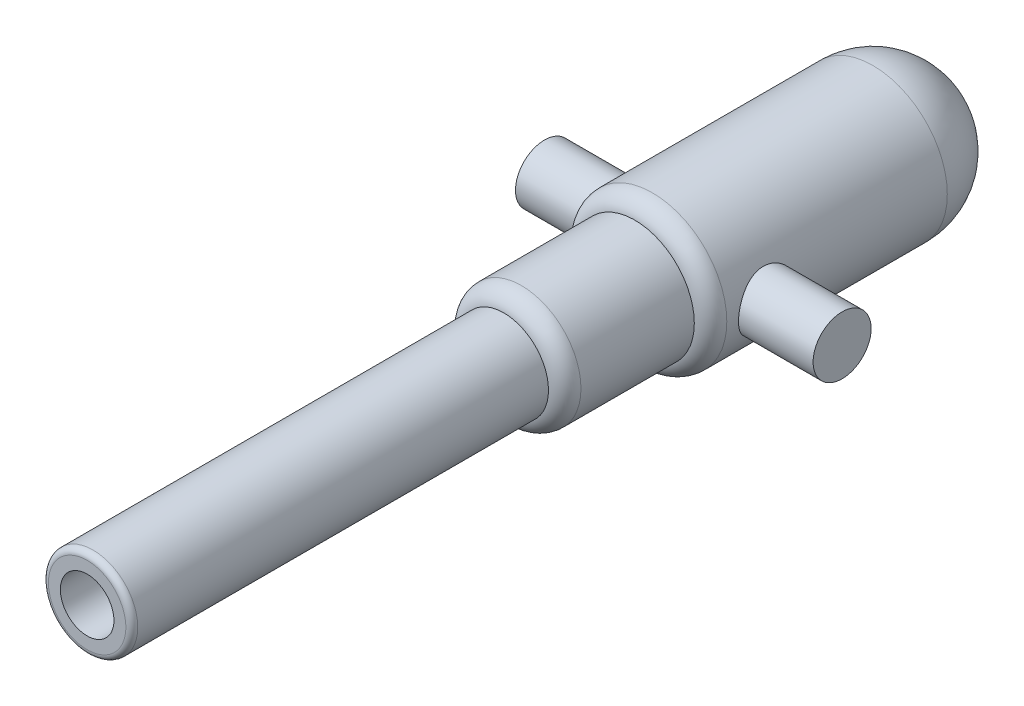
SolidWorks part; units mm, degrees
ref_plane "Front Plane" through (0, 0, 0) normal (0, 0, 1) x (1, 0, 0)
ref_plane "Top Plane" through (0, 0, 0) normal (0, 1, 0) x (1, 0, 0)
ref_plane "Right Plane" through (0, 0, 0) normal (1, 0, 0) x (0, 0, -1)
sketch "Sketch1" plane through (0, 0, 0) normal (1, 0, 0) x (0, 0, -1)
  line L0 (-132, 0) -> (116.6518, 0) construction
  line L1 (0, 12.5) -> (0, 0) construction
  line L2 (0, 12.5) -> (-40, 12.5)
  line L3 (-40, 12.5) -> (-40, 10)
  line L4 (-40, 10) -> (-62, 10)
  line L5 (-62, 10) -> (-62, 7.5)
  line L6 (-62, 7.5) -> (-132, 7.5)
  line L7 (-132, 7.5) -> (-132, 0)
  line L8 (-132, 0) -> (12.5, 0)
  arc A0 (0, 12.5) -> (12.5, 0) centre (0, 0) cw
  dimension "D5" = 12.5
  dimension "D1" = 40
  dimension "D2" = 2.5
  dimension "D3" = 22
  dimension "D4" = 70
revolve "Revolve1" add sketch "Sketch1" angle 360 about L8
fillet "Fillet2" radius 3 2 edges at (12.5, 0, 40) (10, 0, 62)
sketch "Sketch2" plane through (0, 0, 132) normal (0, 0, 1) x (1, 0, 0)
  circle A0 centre (0, 0) radius 4.5
  circle A1 centre (0, 0) radius 7.5
  circle A2 centre (0, 0) radius 7.5
  dimension "D1" = 0
  dimension "D2" = 3
sketch "Sketch3" plane through (0, 0, 0) normal (1, 0, 0) x (0, 0, -1)
  line L0 (-37.1716, 16.5125) -> (-37.1716, -17.7833) construction
  line L1 (-37.1716, -0.6354) -> (30.3277, -0.6354) construction
  circle A0 centre (-30.1716, -0.6354) radius 4.875
  dimension "D1" = 9.75
  dimension "D2" = 7
extrude "Boss-Extrude1" add sketch "Sketch3" along normal blind 25 and the other way blind 25 contours A0
extrude "Cut-Extrude2" cut sketch "Sketch2" against normal blind 120 contours A0
fillet "Fillet3" radius 1 1 edges at (7.5, 0, 132)
